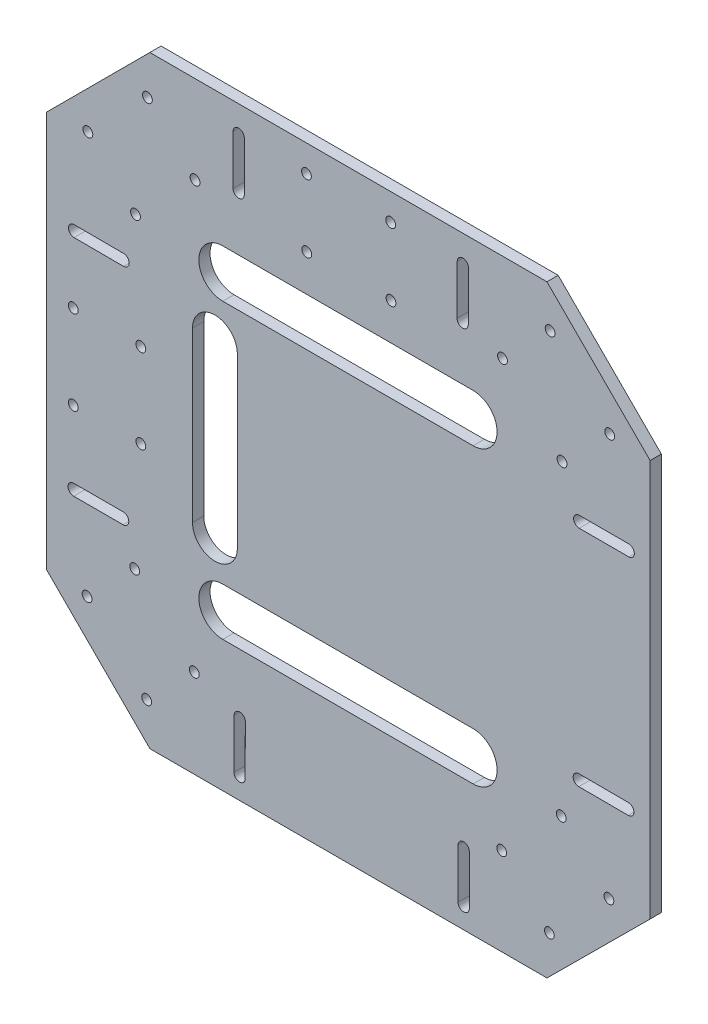
SolidWorks part; units mm, degrees
ref_plane "Front Plane" through (0, 0, 0) normal (0, 0, 1) x (1, 0, 0)
ref_plane "Top Plane" through (0, 0, 0) normal (0, 1, 0) x (1, 0, 0)
ref_plane "Right Plane" through (0, 0, 0) normal (1, 0, 0) x (0, 0, -1)
sketch "Sketch1" plane through (0, 0, 0) normal (0, 0, 1) x (1, 0, 0)
  line L0 (-73.5976, 117.2814) -> (67.8633, 117.2814)
  line L1 (-110.3672, 80.5118) -> (-110.3672, -60.7021)
  line L2 (-73.5668, -97.5025) -> (67.8941, -97.5025)
  line L3 (104.6328, 80.5118) -> (104.6328, -60.9491)
  line L4 (-91.9207, 98.9583) -> (86.2635, -79.2258) construction
  line L5 (-91.9207, -79.1486) -> (86.1863, 98.9583) construction
  line L6 (104.6328, 80.5118) -> (67.8633, 117.2814)
  line L7 (67.8941, -97.5025) -> (104.6328, -60.9491)
  line L8 (-110.3672, -60.7021) -> (-73.5668, -97.5025)
  line L9 (-73.5976, 117.2814) -> (-110.3672, 80.5118)
  line L10 (-106.1246, 84.7545) -> (-77.8403, 113.0387)
  line L11 (-47.6103, 62.0702) -> (41.5768, 62.0702) construction
  line L15 (-47.6103, 70.602) -> (41.5768, 70.602)
  line L16 (-47.6103, 53.5385) -> (41.5768, 53.5385)
  line L19 (-2.8672, 9.9049) -> (-110.3672, 9.9049) construction
  line L20 (-67.3672, 29.5608) -> (-67.3672, -10.4392)
  line L21 (-67.3672, 29.5608) -> (-110.3672, 29.5608)
  line L23 (-92.7181, 99.6354) -> (-92.6579, 99.6956)
  line L25 (-67.3672, -10.4392) -> (-110.3672, -10.4392)
  line L26 (-110.3672, 29.5608) -> (-110.3672, -10.4392)
  line L27 (-67.3672, 29.5608) -> (-110.3672, -10.4392) construction
  line L31 (-67.3672, -10.4392) -> (-110.3672, 29.5608) construction
  line L32 (-110.3672, -10.4392) -> (-110.3672, -5.1592) construction
  line L33 (-110.3672, -5.1592) -> (-100.8667, -5.1592) construction
  line L34 (-110.3672, 80.5118) -> (-110.3672, 9.9049) construction
  line L35 (16.9123, 74.2814) -> (16.9123, 117.2814)
  line L36 (16.9123, 74.2814) -> (-23.0877, 74.2814)
  line L37 (-106.1246, 84.7544) -> (-75.719, 54.3488)
  line L38 (-75.719, 54.3488) -> (-47.4347, 82.6332)
  line L39 (-102.391, 88.488) -> (-95.6735, 81.7705)
  line L40 (41.5768, 82.7567) -> (69.8611, 54.4723)
  line L41 (-77.8403, 113.0387) -> (-75.719, 54.3488) construction
  line L42 (-106.1246, 84.7545) -> (-47.4347, 82.6332) construction
  line L43 (-77.8402, 113.0388) -> (-47.4347, 82.6332)
  line L44 (100.2667, 84.8779) -> (69.8611, 54.4723)
  line L45 (71.9824, 113.1623) -> (41.5768, 82.7567)
  line L46 (69.9846, -34.5391) -> (41.7003, -62.8235)
  line L47 (72.1059, -93.229) -> (41.7003, -62.8235)
  line L48 (100.3902, -64.9447) -> (69.9846, -34.5391)
  line L49 (-47.3112, -62.9469) -> (-75.5955, -34.6626)
  line L50 (-106.0011, -65.0682) -> (-75.5955, -34.6626)
  line L51 (-77.7168, -93.3525) -> (-47.3112, -62.9469)
  line L52 (-23.0877, 74.2814) -> (-23.0877, 117.2814)
  line L53 (-2.8672, 9.7814) -> (-67.3672, 29.5608) construction
  line L54 (-47.6103, -42.2605) -> (41.5768, -42.2605) construction
  line L55 (-47.6103, -50.7923) -> (41.5768, -50.7923)
  line L56 (-47.6103, -33.7287) -> (41.5768, -33.7287)
  line L57 (-50.4034, -20.0951) -> (-50.4034, 39.9049) construction
  line L58 (-67.9409, 117.2814) -> (-3.0009, 117.2814) construction
  line L60 (-67.9409, 117.2814) -> (-50.4034, 117.2814) construction
  line L63 (-110.3672, 39.9049) -> (-110.3672, -20.0951)
  line L64 (-58.3858, -20.0951) -> (-58.3858, 39.9049)
  line L65 (-42.4209, -20.0951) -> (-42.4209, 39.9049)
  line L66 (-41.9513, 90.1358) -> (-41.9513, 107.7809) construction
  line L67 (-43.9513, 90.1358) -> (-43.9513, 107.7809)
  line L68 (-39.9513, 90.1358) -> (-39.9513, 107.7809)
  line L71 (-33.0009, 117.2814) -> (26.9991, 117.2814)
  line L73 (-83.0981, -31.1792) -> (-100.7432, -31.1792) construction
  line L74 (37.8396, 89.9786) -> (37.9109, 107.6236) construction
  line L75 (39.8396, 89.9706) -> (39.9109, 107.6155)
  line L76 (-73.5976, 117.2814) -> (-110.3672, 80.5118)
  line L85 (35.8396, 89.9867) -> (35.9109, 107.6317)
  line L86 (-83.0981, -33.1792) -> (-100.7432, -33.1792)
  line L87 (86.9235, 99.6956) -> (-91.9207, -79.1486) construction
  line L88 (-83.0981, -29.1792) -> (-100.7432, -29.1792)
  line L89 (-91.9207, 98.9583) -> (86.2635, -79.2258) construction
  line L90 (-82.941, 48.6116) -> (-100.5859, 48.6829) construction
  line L91 (-82.9329, 50.6116) -> (-100.5779, 50.6829)
  line L92 (-82.9491, 46.6117) -> (-100.594, 46.683)
  line L93 (38.2169, -72.3261) -> (38.2169, -89.9712) construction
  line L94 (40.2169, -72.3261) -> (40.2169, -89.9712)
  line L95 (36.2169, -72.3261) -> (36.2169, -89.9712)
  line L96 (-41.574, -72.1689) -> (-41.6453, -89.8139) construction
  line L97 (-43.574, -72.1608) -> (-43.6453, -89.8058)
  line L98 (-39.574, -72.177) -> (-39.6453, -89.822)
  line L99 (79.3637, 48.989) -> (97.0088, 48.989) construction
  line L100 (79.3637, 50.989) -> (97.0088, 50.989)
  line L101 (79.3637, 46.989) -> (97.0088, 46.989)
  line L102 (79.2066, -30.8019) -> (96.8515, -30.8732) construction
  line L103 (79.1985, -32.8019) -> (96.8435, -32.8732)
  line L104 (79.2147, -28.8019) -> (96.8596, -28.8732)
  circle A0 centre (-95.6735, 81.7705) radius 1.75
  circle A1 centre (-78.703, 64.7999) radius 1.75
  circle A2 centre (-74.4603, 102.9837) radius 1.75
  circle A3 centre (-57.4898, 86.0131) radius 1.75
  circle A4 centre (73.241, 64.5274) radius 1.75
  circle A5 centre (90.2116, 81.498) radius 1.75
  circle A6 centre (52.0278, 85.7406) radius 1.75
  circle A7 centre (68.9984, 102.7112) radius 1.75
  circle A8 centre (51.7554, -66.2034) radius 1.75
  circle A9 centre (68.7259, -83.174) radius 1.75
  circle A10 centre (72.9686, -44.9902) radius 1.75
  circle A11 centre (89.9391, -61.9607) radius 1.75
  circle A12 centre (-78.9754, -44.7177) radius 1.75
  circle A13 centre (-95.946, -61.6883) radius 1.75
  circle A14 centre (-57.7622, -65.9309) radius 1.75
  circle A15 centre (-74.7328, -82.9015) radius 1.75
  circle A16 centre (-100.8667, -5.1592) radius 1.75
  circle A17 centre (-100.8667, 24.8408) radius 1.75
  circle A18 centre (-76.7981, 24.9643) radius 1.75
  circle A19 centre (-76.7981, -5.0357) radius 1.75
  circle A20 centre (12.1923, 107.7809) radius 1.75
  circle A21 centre (12.3158, 83.7122) radius 1.75
  circle A22 centre (-17.8077, 107.7809) radius 1.75
  circle A23 centre (-17.6842, 83.7122) radius 1.75
  arc A29 (-47.6103, 70.602) -> (-47.6103, 53.5385) centre (-47.6103, 62.0702) ccw
  arc A30 (41.5768, 53.5385) -> (41.5768, 70.602) centre (41.5768, 62.0702) ccw
  arc A31 (-47.6103, -50.7923) -> (-47.6103, -33.7287) centre (-47.6103, -42.2605) cw
  arc A32 (41.5768, -33.7287) -> (41.5768, -50.7923) centre (41.5768, -42.2605) cw
  arc A33 (-58.3858, -20.0951) -> (-42.4209, -20.0951) centre (-50.4034, -20.0951) ccw
  arc A34 (-42.4209, 39.9049) -> (-58.3858, 39.9049) centre (-50.4034, 39.9049) ccw
  arc A35 (-43.9513, 90.1358) -> (-39.9513, 90.1358) centre (-41.9513, 90.1358) ccw
  arc A36 (-39.9513, 107.7809) -> (-43.9513, 107.7809) centre (-41.9513, 107.7809) ccw
  arc A37 (39.8396, 89.9706) -> (35.8396, 89.9867) centre (37.8396, 89.9786) cw
  arc A38 (35.9109, 107.6317) -> (39.9109, 107.6155) centre (37.9109, 107.6236) cw
  arc A39 (-83.0981, -33.1792) -> (-83.0981, -29.1792) centre (-83.0981, -31.1792) ccw
  arc A40 (-100.7432, -29.1792) -> (-100.7432, -33.1792) centre (-100.7432, -31.1792) ccw
  arc A41 (-82.9329, 50.6116) -> (-82.9491, 46.6117) centre (-82.941, 48.6116) cw
  arc A42 (-100.594, 46.683) -> (-100.5779, 50.6829) centre (-100.5859, 48.6829) cw
  arc A43 (40.2169, -72.3261) -> (36.2169, -72.3261) centre (38.2169, -72.3261) ccw
  arc A44 (36.2169, -89.9712) -> (40.2169, -89.9712) centre (38.2169, -89.9712) ccw
  arc A45 (-43.574, -72.1608) -> (-39.574, -72.177) centre (-41.574, -72.1689) cw
  arc A46 (-39.6453, -89.822) -> (-43.6453, -89.8058) centre (-41.6453, -89.8139) cw
  arc A47 (79.3637, 50.989) -> (79.3637, 46.989) centre (79.3637, 48.989) ccw
  arc A48 (97.0088, 46.989) -> (97.0088, 50.989) centre (97.0088, 48.989) ccw
  arc A49 (79.1985, -32.8019) -> (79.2147, -28.8019) centre (79.2066, -30.8019) cw
  arc A50 (96.8596, -28.8732) -> (96.8435, -32.8732) centre (96.8515, -30.8732) cw
  point P0 (-2.8672, 9.9049)
  point P8 (-91.9824, 99.0201)
  point P17 (-2.8672, 9.9049)
  point P18 (-91.9824, 98.8966)
  point P33 (-2.8672, 9.9049)
  point P35 (-3.0168, 62.0702)
  point P38 (-120.1149, 127.1526)
  point P41 (-120.9422, 9.9076)
  point P45 (-88.8672, 9.5608)
  point P74 (-3.0168, -42.2605)
  point P85 (-50.4034, 9.9049)
  point P95 (-3.0168, 9.9309)
  point P97 (-41.9513, 98.9583)
  point P142 (37.8752, 98.8011)
  point P145 (-2.8672, 9.9049)
  point P152 (-91.9207, -31.1792)
  point P159 (-91.7635, 48.6473)
  point P166 (38.2169, -81.1486)
  point P173 (-41.6096, -80.9914)
  point P180 (88.1863, 48.989)
  point P187 (88.0291, -30.8376)
  point P192 (-1.8672, 8.9049)
  dimension "D7" = 3.5
  dimension "D10" = 3.5
  dimension "D13" = 3.5
  dimension "D19" = 2
  dimension "D20" = 4
  dimension "D22" = 2
  dimension "D1" = 52
  dimension "D2" = 141.4609
  dimension "D3" = 215
  dimension "D4" = 40
  dimension "D5" = 9.5
  dimension "D6" = 5.28
  dimension "D8" = 24
  dimension "D9" = 43
  dimension "D11" = 30
  dimension "D12" = 30
  dimension "D14" = 43
  dimension "D15" = 5.28
  dimension "D16" = 30
  dimension "D17" = 67.4646
  dimension "D18" = 17.5375
  dimension "D21" = 64.94
extrude "Boss-Extrude2" add sketch "Sketch1" along normal blind 4 contours L36 L52 L0 L9 L43 L38 L37 L1 L21 L20 L25 L8 L50 L49 L51 L2 L7 L3 L6 L44 L40 L45 L35 A48 L101 A47 L100 A44 L95 A43 L94 A40 | L6 L45 L40 L44 A7 A6 A5 A4 | L52 L36 L35 L0 A23 A22 A21 A20 | A0 L10 L9 L37 L38 L43 A3 A2 A1 | L25 L20 L21 L1 A19 A18 A17 A16 | L8 L51 L49 L50 A15 A14 A13 A12 region at (8.2467, 0.7071, 0) region at (-76.7842, 83.6893, 0) region at (-3.0955, 95.7822, 0) region at (70.9172, 83.8218, 0) region at (-88.868, 9.553, 0) region at (-76.6516, -64.0121, 0)
